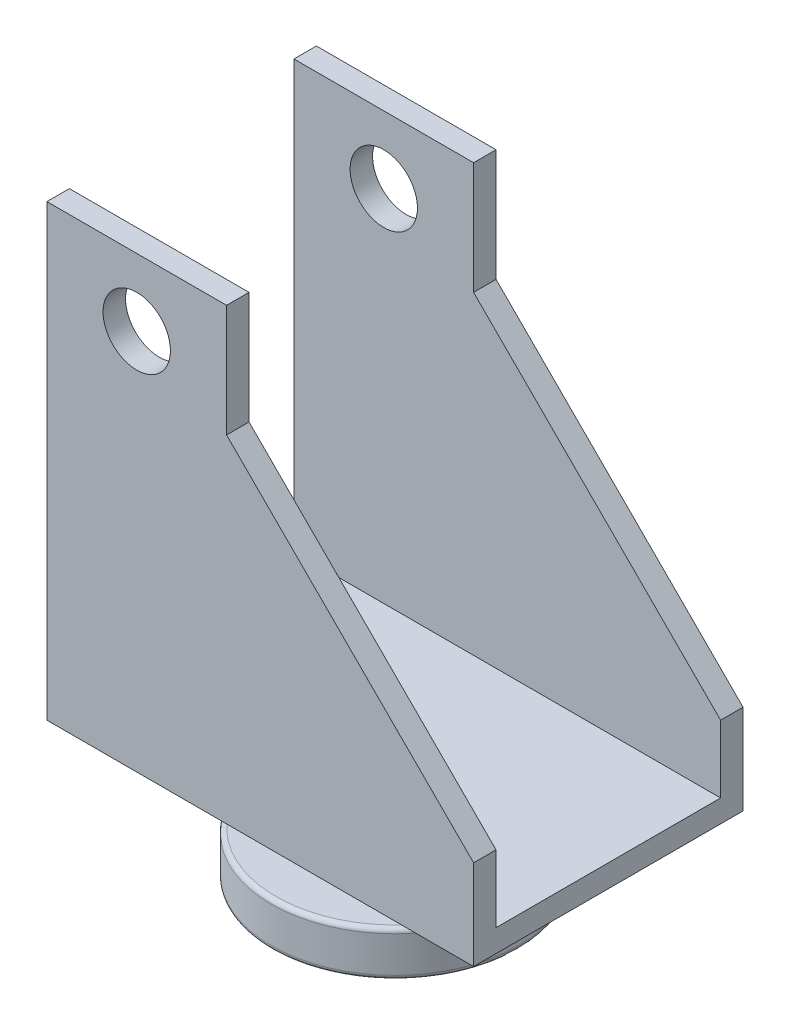
SolidWorks part; units mm, degrees
material "1060 Alloy"
ref_plane "Front Plane" through (0, 0, 0) normal (0, 0, 1) x (1, 0, 0)
ref_plane "Top Plane" through (0, 0, 0) normal (0, 1, 0) x (1, 0, 0)
ref_plane "Right Plane" through (0, 0, 0) normal (1, 0, 0) x (0, 0, -1)
sketch "Sketch1" plane through (0, 0, 0) normal (0, 0, 1) x (1, 0, 0)
  line L0 (0, 0) -> (95, 0)
  line L1 (95, 0) -> (95, 20)
  line L2 (95, 20) -> (40, 75)
  line L3 (40, 75) -> (40, 100)
  line L4 (40, 100) -> (0, 100)
  line L5 (0, 100) -> (0, 0)
  circle A0 centre (20, 85) radius 7.5
  point P10 (20, 100)
  dimension "D6" = 15
  dimension "D1" = 100
  dimension "D2" = 40
  dimension "D3" = 25
  dimension "D4" = 135
  dimension "D5" = 20
  dimension "D7" = 85
extrude "Boss-Extrude1" add sketch "Sketch1" along normal mid plane 60 contours L4 L5 L0 L1 L2 L3 A0 | A0 region at (37.1275, 39.4604, 0) region at (20, 85, 0)
shell "Shell1" thickness 5 removed face at (0, 50, 0) removed face at (95, 10, 0) removed face at (40, 87.5, 0) removed face at (20, 100, 0) removed face at (67.5, 47.5, 0)
extrude "Cut-Extrude1" cut sketch "Sketch1<3>" against normal through all both and the other way through all contours A0
sketch "Sketch1<3>" plane through (0, 0, 0) normal (0, 0, 1) x (1, 0, 0) same geometry as "Sketch1"
sketch "Sketch2" plane through (0, 0, 0) normal (0, -1, 0) x (1, 0, 0)
  line L1 (0, -30) -> (95, -30) construction
  circle A0 centre (47.5, 0) radius 15
  point P7 (47.5, -30)
  dimension "D1" = 30
extrude "Boss-Extrude2" add sketch "Sketch2" along normal blind 12
sketch "Sketch3" plane through (0, -12, 0) normal (0, -1, 0) x (1, 0, 0)
  circle A0 centre (47.5, 0) radius 27.5
  dimension "D1" = 55
extrude "Boss-Extrude3" add sketch "Sketch3" along normal blind 10
fillet "Fillet1" radius 1 2 edges at (47.5, -22, -27.5) (47.5, -12, -27.5)
